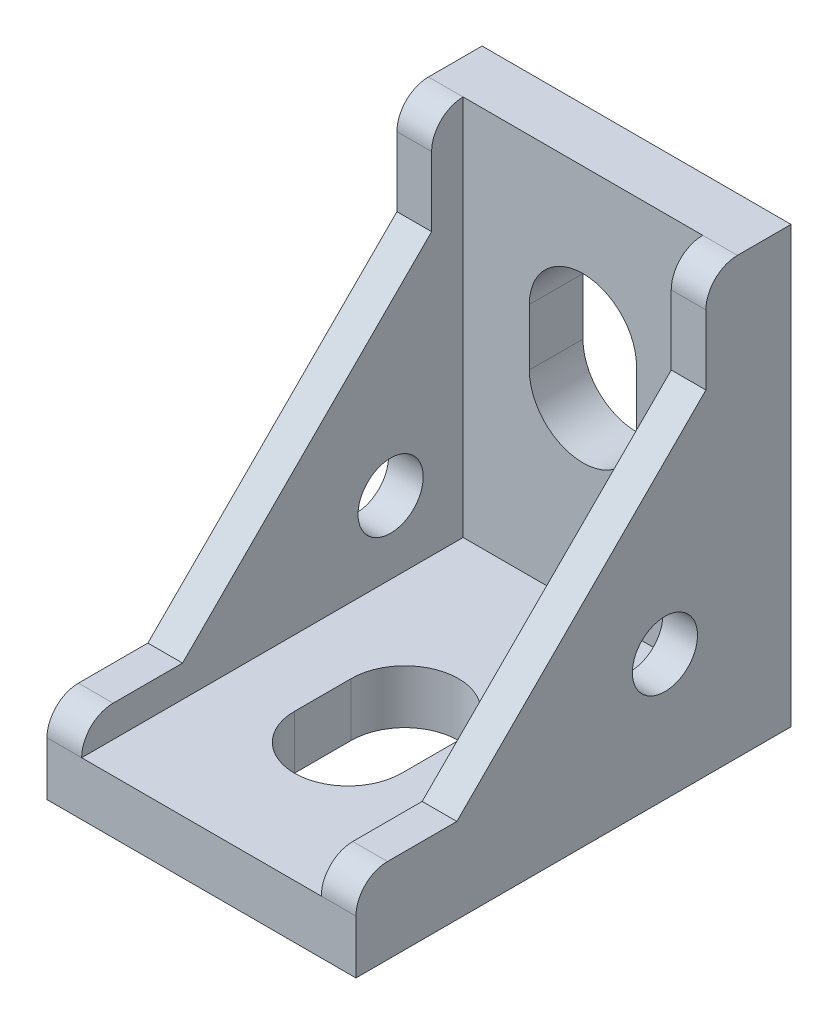
SolidWorks part; units mm, degrees
ref_plane "Front Plane" through (0, 0, 0) normal (0, 0, 1) x (1, 0, 0)
ref_plane "Top Plane" through (0, 0, 0) normal (0, 1, 0) x (1, 0, 0)
ref_plane "Right Plane" through (0, 0, 0) normal (1, 0, 0) x (0, 0, -1)
ref_axis "Axis_X" through (-10.78, 0, 0) along (1, 0, 0)
ref_axis "Axis_Y" through (0, 29.08, 0) along (0, -1, 0)
ref_axis "Axis_Z" through (0, 0, -3.48) along (0, 0, 1)
sketch "Sketch1" plane through (0, 0, 0) normal (1, 0, 0) x (0, 0, -1)
  line L1 (0, 0) -> (-27.6, 0)
  line L2 (0, 0) -> (0, 27.6)
  line L3 (0, 27.6) -> (-27.6, 27.6)
  line L4 (-27.6, 0) -> (-27.6, 27.6)
  dimension "H" = 27.6
extrude "Boss-Extrude1" add sketch "Sketch1" along normal mid plane 19.6
sketch "Sketch2" plane through (-9.8, 0, 0) normal (-1, 0, 0) x (0, 0, 1)
  line L0 (27.6, 27.6) -> (5.4, 27.6)
  line L1 (0, 27.6) -> (27.6, 27.6) construction
  line L2 (5.4, 27.6) -> (27.6, 5.4)
  line L3 (27.6, 27.6) -> (27.6, 0) construction
  line L4 (27.6, 5.4) -> (27.6, 27.6)
  line L5 (0, 0) -> (0, 27.6) construction
  dimension "W1" = 5.4
extrude "Cut-Extrude1" cut sketch "Sketch2" against normal through all
sketch "Sketch3" plane through (0, 27.6, 0) normal (0, 1, 0) x (1, 0, 0)
  line L0 (9.8, -27.6) -> (-9.8, -27.6) construction
  line L1 (-7.6, -27.6) -> (7.6, -27.6)
  line L2 (-7.6, -27.6) -> (-7.6, -3.4)
  line L3 (-7.6, -3.4) -> (7.6, -3.4)
  line L4 (7.6, -27.6) -> (7.6, -3.4)
  line L5 (0, 0) -> (0, -3.4) construction
  line L6 (9.8, 0) -> (-9.8, 0) construction
  line L7 (-9.8, 0) -> (-9.8, -5.4) construction
  dimension "T" = 3.4
  dimension "T1" = 2.2
extrude "Cut-Extrude2" cut sketch "Sketch3" against normal offset from surface (24.2 mm away) 3.4 up to face at (0, 0, 13.8)
sketch "Sketch4" plane through (-9.8, 0, 0) normal (-1, 0, 0) x (0, 0, 1)
  line L0 (5.4, 27.6) -> (5.4, 21.2)
  line L1 (5.4, 21.2) -> (21.2, 5.4)
  line L2 (21.2, 5.4) -> (27.6, 5.4)
  line L3 (0, 0) -> (0, 27.6) construction
  line L4 (0, 27.6) -> (5.4, 27.6) construction
  line L5 (27.6, 5.4) -> (27.6, 0) construction
  line L6 (5.4, 27.6) -> (27.6, 5.4)
  dimension "W1" = 5.4
  dimension "FIX_1" = 6.4
extrude "Cut-Extrude3" cut sketch "Sketch4" against normal through all
fillet "Fillet110" radius 2 4 edges at (8.7, 5.4, 27.6) (-8.7, 5.4, 27.6) (8.7, 27.6, 5.4) (-8.7, 27.6, 5.4)
sketch "Sketch5" plane through (0, 0, 3.4) normal (0, 0, 1) x (1, 0, 0)
  line L0 (0, 14.7) -> (0, 18.3) construction
  line L1 (-3.4, 14.7) -> (-3.4, 18.3)
  line L2 (3.4, 14.7) -> (3.4, 18.3)
  line L3 (9.8, 0) -> (-9.8, 0) construction
  arc A0 (-3.4, 14.7) -> (3.4, 14.7) centre (0, 14.7) ccw
  arc A1 (3.4, 18.3) -> (-3.4, 18.3) centre (0, 18.3) ccw
  point P2 (0, 16.5)
  dimension "R" = 3.4
  dimension "B" = 3.6
  dimension "A" = 14.7
extrude "Cut-Extrude4" cut sketch "Sketch5" against normal through all
sketch "Sketch6" plane through (0, 3.4, 0) normal (0, 1, 0) x (1, 0, 0)
  line L0 (0, -14.7) -> (0, -18.3) construction
  line L1 (3.4, -14.7) -> (3.4, -18.3)
  line L2 (-3.4, -14.7) -> (-3.4, -18.3)
  line L3 (9.8, 0) -> (-9.8, 0) construction
  arc A0 (3.4, -14.7) -> (-3.4, -14.7) centre (0, -14.7) ccw
  arc A1 (-3.4, -18.3) -> (3.4, -18.3) centre (0, -18.3) ccw
  point P2 (0, -16.5)
  dimension "R" = 3.4
  dimension "B" = 3.6
  dimension "A" = 14.7
extrude "Cut-Extrude5" cut sketch "Sketch6" against normal through all
sketch "Sketch7" plane through (0, 0, 0) normal (0, 0, -1) x (-1, 0, 0)
  line L0 (0, 27.6) -> (0, 0) construction
  line L1 (-2.9, 26.1) -> (2.9, 26.1)
  line L2 (-2.9, 26.1) -> (-2.9, 23.1)
  line L3 (-2.9, 23.1) -> (2.9, 23.1)
  line L4 (2.9, 26.1) -> (2.9, 23.1)
  line L5 (-2.9, 4.5) -> (2.9, 4.5)
  line L6 (-2.9, 4.5) -> (-2.9, 1.5)
  line L7 (-2.9, 1.5) -> (2.9, 1.5)
  line L8 (2.9, 4.5) -> (2.9, 1.5)
  line L9 (-9.8, 27.6) -> (9.8, 27.6) construction
  line L10 (-9.8, 0) -> (9.8, 0) construction
  dimension "W" = 5.8
  dimension "MSM_1" = 3
extrude "Boss-Extrude2" add sketch "Sketch7" along normal blind 2
sketch "Sketch8" plane through (0, 0, 0) normal (0, -1, 0) x (1, 0, 0)
  line L0 (0, 0) -> (0, 27.6) construction
  line L1 (-2.9, 26.1) -> (2.9, 26.1)
  line L2 (-2.9, 26.1) -> (-2.9, 23.1)
  line L3 (-2.9, 23.1) -> (2.9, 23.1)
  line L4 (2.9, 26.1) -> (2.9, 23.1)
  line L5 (-2.9, 4.5) -> (2.9, 4.5)
  line L6 (-2.9, 4.5) -> (-2.9, 1.5)
  line L7 (-2.9, 1.5) -> (2.9, 1.5)
  line L8 (2.9, 4.5) -> (2.9, 1.5)
  line L9 (9.8, 27.6) -> (-9.8, 27.6) construction
  line L10 (9.8, 0) -> (-9.8, 0) construction
  dimension "W" = 5.8
  dimension "MSM_1" = 3
extrude "Boss-Extrude3" add sketch "Sketch8" along normal blind 2
sketch "Sketch9" plane through (2.9, 0, 0) normal (1, 0, 0) x (0, 0, -1)
  line L0 (0, 26.1) -> (2, 23.6)
  line L1 (2, 26.1) -> (2, 23.1) construction
  line L2 (2, 23.6) -> (2, 26.1)
  line L3 (2, 26.1) -> (0, 26.1)
  line L4 (2, 23.1) -> (0, 23.1) construction
  line L5 (0, 4.5) -> (2, 4.5)
  line L6 (2, 4.5) -> (2, 2)
  line L7 (2, 4.5) -> (2, 1.5) construction
  line L8 (2, 2) -> (0, 4.5)
  line L9 (-26.1, 0) -> (-26.1, -2)
  line L10 (-26.1, -2) -> (-23.6, -2)
  line L11 (-23.1, -2) -> (-26.1, -2) construction
  line L12 (-23.6, -2) -> (-26.1, 0)
  line L13 (-4.5, 0) -> (-4.5, -2)
  line L14 (-4.5, -2) -> (-2, -2)
  line L15 (-1.5, -2) -> (-4.5, -2) construction
  line L16 (-2, -2) -> (-4.5, 0)
  dimension "FIX_5" = 0.5
extrude "Cut-Extrude6" cut sketch "Sketch9" against normal through all
hole_wizard "Tap101" positions "Sketch11" profile "Sketch10" hole size "M5x0.8" standard "JIS" end condition through all
sketch "Sketch11" plane through (-9.8, 0, 0) normal (-1, 0, 0) x (0, 0, 1)
  line L0 (27.6, 0) -> (0, 0) construction
  line L1 (0, 0) -> (0, 27.6) construction
  point P0 (8, 8)
sketch "Sketch10" plane through (-9.8, 8, 8) normal (0, 1, 0) x (0, 0, 1)
  line L0 (0, 0) -> (0, 19.6)
  line L1 (0, 19.6) -> (2.067, 19.6)
  line L2 (2.067, 19.6) -> (2.067, 0)
  line L5 (2.067, 0) -> (0, 0)
  line L11 (0, -6.35) -> (0, 107.95) construction
  dimension "FIX_3" = 4.134
  dimension "Thru Hole Depth" = 19.6
cosmetic thread "Thread1" parameters "FIX_4"=5
sketch "Sketch12" plane through (0, 0, 0) normal (1, 0, 0) x (0, 0, -1)
  line L0 (0, 26.1) -> (2, 23.6) construction
  line L1 (0, 23.1) -> (2, 23.1)
  line L2 (0, 23.1) -> (0, 26.1)
  line L3 (0, 26.1) -> (2, 26.1)
  line L4 (2, 23.1) -> (2, 26.1)
  line L5 (0, 4.5) -> (0, 1.5) construction
  line L6 (0, 1.5) -> (2, 1.5)
  line L7 (0, 1.5) -> (0, 4.5)
  line L8 (0, 4.5) -> (2, 4.5)
  line L9 (2, 1.5) -> (2, 4.5)
  line L10 (0, 4.5) -> (2, 2) construction
  line L11 (-23.6, -2) -> (-26.1, 0) construction
  line L12 (-1.5, 0) -> (-4.5, 0)
  line L13 (-1.5, 0) -> (-1.5, -2)
  line L14 (-1.5, -2) -> (-4.5, -2)
  line L15 (-4.5, 0) -> (-4.5, -2)
  line L16 (-23.1, 0) -> (-26.1, 0)
  line L17 (-23.1, 0) -> (-23.1, -2)
  line L18 (-23.1, -2) -> (-26.1, -2)
  line L19 (-26.1, 0) -> (-26.1, -2)
  line L20 (-27.6, 0) -> (0, 0) construction
extrude "Cut-Extrude110" [suppressed] cut sketch "Sketch12" against normal mid plane 3
sketch "Sketch13" plane through (0, 0, 0) normal (1, 0, 0) x (0, 0, -1)
  line L1 (-10, 0) -> (0, 0)
  line L2 (-27.6, 0) -> (0, 0) construction
  line L3 (0, 0) -> (0, 10)
  line L4 (0, 0) -> (0, 27.6) construction
  line L6 (0, 10) -> (10, 10)
  line L7 (10, 10) -> (10, -10)
  line L8 (10, -10) -> (-10, -10)
  line L9 (-10, -10) -> (-10, 0)
  dimension "D1" = 10
  dimension "D2" = 10
extrude "Cut-Extrude111" [suppressed] cut sketch "Sketch13" against normal through all both and the other way through all
sketch "Sketch14" plane through (0, 0, 0) normal (1, 0, 0) x (0, 0, -1)
  line L0 (-4.4, 0) -> (-0.9, 0)
  line L1 (-27.6, 0) -> (0, 0) construction
  line L2 (1.3129, -3.3) -> (0.6282, -3.3)
  line L3 (0.0546, -3.1192) -> (-4.4, 0)
  line L4 (0, 4.4) -> (0, 0.9)
  line L5 (0, 0) -> (0, 27.6) construction
  line L6 (3.3, -0.6282) -> (3.3, -1.3129)
  line L7 (3.1192, -0.0546) -> (0, 4.4)
  line L10 (1.3129, -3.3) -> (-0.9, 0)
  line L11 (3.3, -1.3129) -> (0, 0.9)
  arc A0 (0.6282, -3.3) -> (0.0546, -3.1192) centre (0.6282, -2.3) cw
  arc A1 (3.3, -0.6282) -> (3.1192, -0.0546) centre (2.3, -0.6282) ccw
  point P14 (0.3129, -3.3)
  point P18 (3.3, -0.3129)
  dimension "D10" = 1
  dimension "D12" = 1
  dimension "D1" = 3.3
  dimension "D2" = 3.3
  dimension "D3" = 3.5
  dimension "D4" = 3.5
  dimension "D5" = 35
  dimension "D6" = 35
  dimension "D7" = 4.4
  dimension "D8" = 4.4
  dimension "D9" = 1
  dimension "D11" = 1
extrude "Boss-Extrude111" [suppressed] add sketch "Sketch14" along normal mid plane 7.8
sketch "Sketch15" plane through (0, 0, 0) normal (1, 0, 0) x (0, 0, -1)
  line L8 (0, 0) -> (-10, 0)
  line L9 (0, 10) -> (0, 0)
  line L10 (10, 10) -> (0, 10)
  line L11 (10, -10) -> (10, 10)
  line L12 (-10, -10) -> (10, -10)
  line L13 (-10, 0) -> (-10, -10)
  line L14 (0, 0) -> (-10, 0)
  line L15 (0, 10) -> (0, 0)
  line L16 (10, 10) -> (0, 10)
  line L17 (10, -10) -> (10, 10)
  line L18 (-10, -10) -> (10, -10)
  line L19 (-10, 0) -> (-10, -10)
  dimension "D1" = 0
extrude "Cut-Extrude112" [suppressed] cut sketch "Sketch15" against normal mid plane 3
fillet "Fillet111" [suppressed] radius 0.4
fillet "Fillet112" [suppressed] radius 0.3
equation "\"Factor\"= 1.082532"
